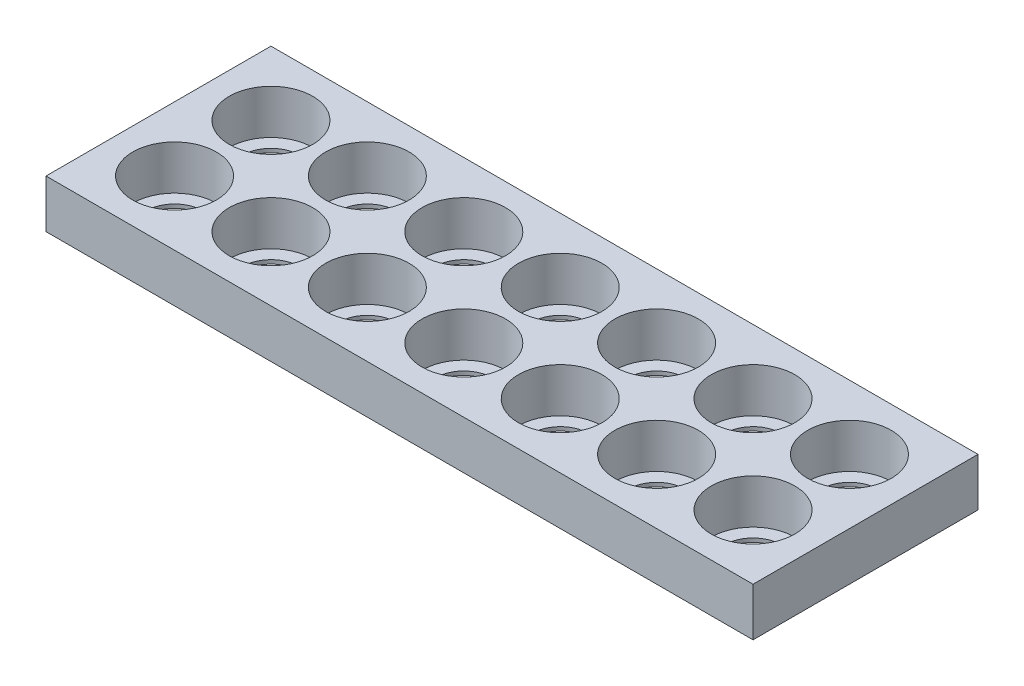
SolidWorks part; units mm, degrees
ref_plane "Front Plane" through (0, 0, 0) normal (0, 0, 1) x (1, 0, 0)
ref_plane "Top Plane" through (0, 0, 0) normal (0, 1, 0) x (1, 0, 0)
ref_plane "Right Plane" through (0, 0, 0) normal (1, 0, 0) x (0, 0, -1)
sketch "Sketch1" plane through (0, 0, 0) normal (0, 1, 0) x (1, 0, 0)
  line L1 (-16.9333, -16.9333) -> (169.3333, -16.9333)
  line L2 (-16.9333, -16.9333) -> (-16.9333, 42.3333)
  line L3 (-16.9333, 42.3333) -> (169.3333, 42.3333)
  line L4 (169.3333, -16.9333) -> (169.3333, 42.3333)
  circle A0 centre (0, 0) radius 10.9982
  circle A1 centre (0, 0) radius 7.5
  circle A2 centre (25.4, 0) radius 10.9982
  circle A3 centre (25.4, 0) radius 7.5
  circle A4 centre (50.8, 0) radius 10.9982
  circle A5 centre (50.8, 0) radius 7.5
  circle A6 centre (76.2, 0) radius 10.9982
  circle A7 centre (76.2, 0) radius 7.5
  circle A8 centre (101.6, 0) radius 10.9982
  circle A9 centre (101.6, 0) radius 7.5
  circle A10 centre (127, 0) radius 10.9982
  circle A11 centre (127, 0) radius 7.5
  circle A12 centre (152.4, 0) radius 10.9982
  circle A13 centre (152.4, 0) radius 7.5
  circle A14 centre (25.4, 25.4) radius 10.9982
  circle A15 centre (25.4, 25.4) radius 7.5
  circle A16 centre (50.8, 25.4) radius 10.9982
  circle A17 centre (50.8, 25.4) radius 7.5
  circle A18 centre (76.2, 25.4) radius 10.9982
  circle A19 centre (76.2, 25.4) radius 7.5
  circle A20 centre (101.6, 25.4) radius 10.9982
  circle A21 centre (101.6, 25.4) radius 7.5
  circle A22 centre (127, 25.4) radius 10.9982
  circle A23 centre (127, 25.4) radius 7.5
  circle A24 centre (152.4, 25.4) radius 10.9982
  circle A25 centre (152.4, 25.4) radius 7.5
  circle A26 centre (0, 25.4) radius 10.9982
  circle A27 centre (0, 25.4) radius 7.5
  point P4 (0, 0)
  point P5 (0, 0)
  point P6 (0, 0)
  point P50 (0, 0)
  point P51 (0, 0)
  point P52 (0, 0)
  point P53 (0, 0)
  point P54 (0, 0)
  point P55 (0, 0)
  point P56 (0, 0)
  dimension "D1" = 21.9964
  dimension "D2" = 15
  dimension "D5" = 16.9333
  dimension "D7" = 16.9333
  dimension "D8" = 16.9333
  dimension "D6" = 16.9333
  dimension "D3" = 7
  dimension "D4" = 2
extrude "Boss-Extrude2" add sketch "Sketch1" along normal blind 12.7 contours L1 L4 L3 L2 A26 A24 A22 A20 A18 A16 A14 A12 A10 A8 A6 A4 A2 A0 region at (76.2, 0, -12.7)
extrude "Boss-Extrude3" add sketch "Sketch1<4>" along normal blind 1.016 contours A26 A27 | A14 A15 | A16 A17 | A18 A19 | A20 A21 | A22 A23 | A24 A25 | A0 A1 | A2 A3 | A4 A5 | A6 A7 | A8 A9 | A10 A11 | A12 A13 region at (-10.6871, 0, 0) region at (14.7129, 0, 0) region at (40.1129, 0, 0) region at (65.5129, 0, 0) region at (90.9129, 0, 0) region at (116.3129, 0, 0) region at (141.7129, 0, 0) region at (14.7129, 0, -25.4) region at (40.1129, 0, -25.4) region at (65.5129, 0, -25.4) region at (90.9129, 0, -25.4) region at (116.3129, 0, -25.4) region at (141.7129, 0, -25.4) region at (-10.6871, 0, -25.4)
sketch "Sketch1<4>" plane through (0, 0, 0) normal (0, 1, 0) x (1, 0, 0) same geometry as "Sketch1"
